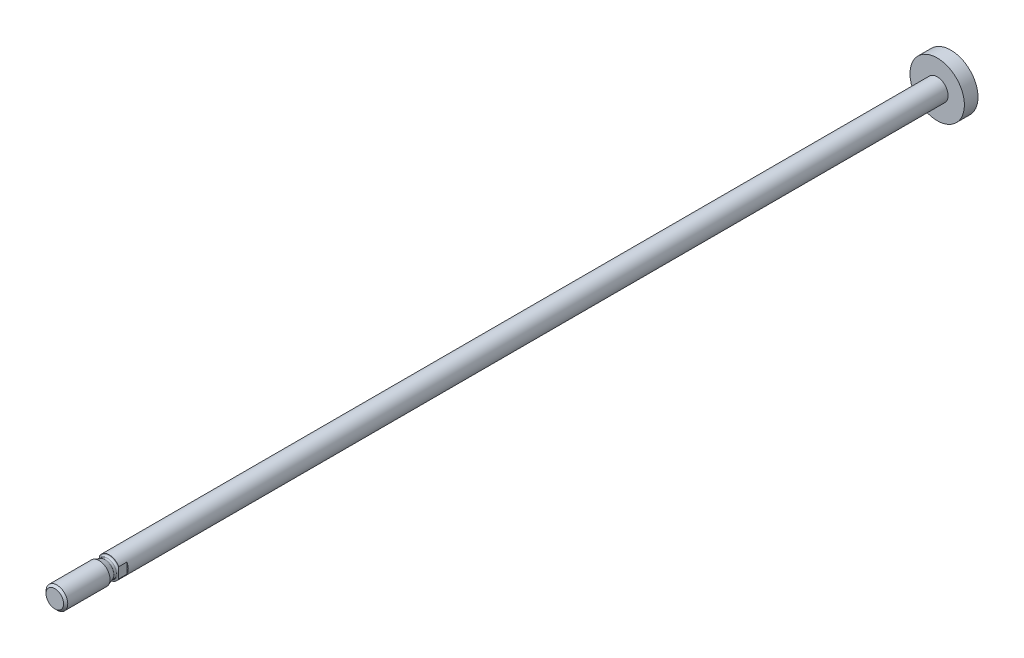
SolidWorks part; units mm, degrees
ref_plane "Front Plane" through (0, 0, 0) normal (0, 0, 1) x (1, 0, 0)
ref_plane "Top Plane" through (0, 0, 0) normal (0, 1, 0) x (1, 0, 0)
ref_plane "Right Plane" through (0, 0, 0) normal (1, 0, 0) x (0, 0, -1)
sketch "Sketch1" plane through (0, 0, 0) normal (1, 0, 0) x (0, 0, -1)
  line L0 (-4, 0) -> (-4, 4)
  line L1 (-4, 4) -> (300.3, 4)
  line L2 (300.3, 4) -> (300.3, 10)
  line L3 (300.3, 10) -> (305.3, 10)
  line L4 (305.3, 10) -> (305.3, 0)
  line L5 (305.3, 0) -> (-4, 0)
  line L6 (305.3, 0) -> (-4, 0) construction
revolve "Revolve1" add sketch "Sketch1" angle 360 about L6 reverse direction yes
sketch "Sketch2" plane through (0, 0, 0) normal (1, 0, 0) x (0, 0, -1)
  line L0 (-24, 0) -> (-24, 3.233)
  line L1 (-24, 3.233) -> (-23.233, 4)
  line L2 (-23.233, 4) -> (-7.698, 4)
  line L3 (-7.698, 4) -> (-5.5994, 3.2362)
  line L4 (-5.3942, 3.2) -> (-4.6, 3.2)
  line L5 (-4, 3.8) -> (-4, 4)
  line L6 (-4, 4) -> (-3, 4)
  line L7 (-3, 4) -> (-3, 0)
  line L8 (-3, 0) -> (-24, 0)
  line L9 (-3, 0) -> (-24, 0) construction
  arc A0 (-5.5994, 3.2362) -> (-5.3942, 3.2) centre (-5.3942, 3.8) ccw
  arc A1 (-4.6, 3.2) -> (-4, 3.8) centre (-4.6, 3.8) ccw
revolve "Revolve2" add sketch "Sketch2" angle 360 about L9 reverse direction yes
cosmetic thread "Cosmetic Thread1" parameters "D1"=16.302, "D2"=6.466
ref_plane "Plane1" through (0, 0, 4) normal (0, 0, 1) x (1, 0, 0)
ref_plane "Plane2" through (0, 0, 1) normal (0, 0, 1) x (1, 0, 0)
sketch "Sketch3" plane through (0, 0, 1) normal (0, 0, 1) x (1, 0, 0)
  line L0 (-7, 14) -> (-7, -7)
  line L1 (-7, -7) -> (-3.5, -7)
  line L2 (-3.5, -7) -> (-3.5, 7)
  line L3 (-3.5, 7) -> (3.5, 7)
  line L4 (3.5, 7) -> (3.5, -7)
  line L5 (3.5, -7) -> (7, -7)
  line L6 (7, -7) -> (7, 14)
  line L7 (7, 14) -> (-7, 14)
extrude "Cut-Extrude1" cut sketch "Sketch3" along normal blind 4
ref_plane "Plane3" through (0, 0, -612) normal (0, 0, 1) x (1, 0, 0)
ref_plane "Plane4" through (0, 0, 20) normal (0, 0, 1) x (1, 0, 0)
ref_plane "Plane5" through (0, 0, 12) normal (0, 0, 1) x (1, 0, 0)
ref_plane "FDT_KSAUFSATZ XY" through (0, 0, 12) normal (0, 0, 1) x (1, 0, 0)
ref_plane "FDT_KSAUFSATZ XZ" through (0, 0, 0) normal (0, 1, 0) x (1, 0, 0)
ref_plane "FDT_KSAUFSATZ YZ" through (0, 0, 0) normal (-1, 0, 0) x (0, 0, 1)
ref_axis "FDT_KSAUFSATZ X" through (80.9, 0, 12) along (-1, 0, 0)
ref_axis "FDT_KSAUFSATZ Y" through (0, 50, 12) along (0, -1, 0)
ref_axis "FDT_KSAUFSATZ Z" through (0, 0, 80.9) along (0, 0, -1)
sketch3d "FDT_KSAUFSATZ"
  point P0 (0, 0, 12)
ref_plane "FDT_NUT XY" through (0, 0, 12) normal (0, 0, 1) x (1, 0, 0)
ref_plane "FDT_NUT XZ" through (0, 0, 0) normal (0, 1, 0) x (1, 0, 0)
ref_plane "FDT_NUT YZ" through (0, 0, 0) normal (-1, 0, 0) x (0, 0, 1)
ref_axis "FDT_NUT X" through (80.9, 0, 12) along (-1, 0, 0)
ref_axis "FDT_NUT Y" through (0, 50, 12) along (0, -1, 0)
ref_axis "FDT_NUT Z" through (0, 0, 80.9) along (0, 0, -1)
sketch3d "FDT_NUT"
  point P0 (0, 0, 12)
ref_plane "KS XY" through (0, 0, 0) normal (0, 0, -1) x (-1, 0, 0)
ref_plane "KS XZ" through (0, 0, 0) normal (0, 1, 0) x (1, 0, 0)
ref_plane "KS YZ" through (0, 0, 0) normal (1, 0, 0) x (0, 0, -1)
ref_axis "KS X" through (-80.9, 0, 0) along (1, 0, 0)
ref_axis "KS Y" through (0, 50, 0) along (0, -1, 0)
ref_axis "KS Z" through (0, 0, -80.9) along (0, 0, 1)
sketch3d "KS"
  point P0 (0, 0, 0)
ref_plane "NUT1 XY" through (0, 0, 20) normal (0, 0, 1) x (1, 0, 0)
ref_plane "NUT1 XZ" through (0, 0, 0) normal (0, -1, 0) x (-1, 0, 0)
ref_plane "NUT1 YZ" through (0, 0, 0) normal (1, 0, 0) x (0, 0, -1)
ref_axis "NUT1 X" through (-80.9, 0, 20) along (1, 0, 0)
ref_axis "NUT1 Y" through (0, -50, 20) along (0, 1, 0)
ref_axis "NUT1 Z" through (0, 0, 80.9) along (0, 0, -1)
sketch3d "NUT1"
  point P0 (0, 0, 20)
